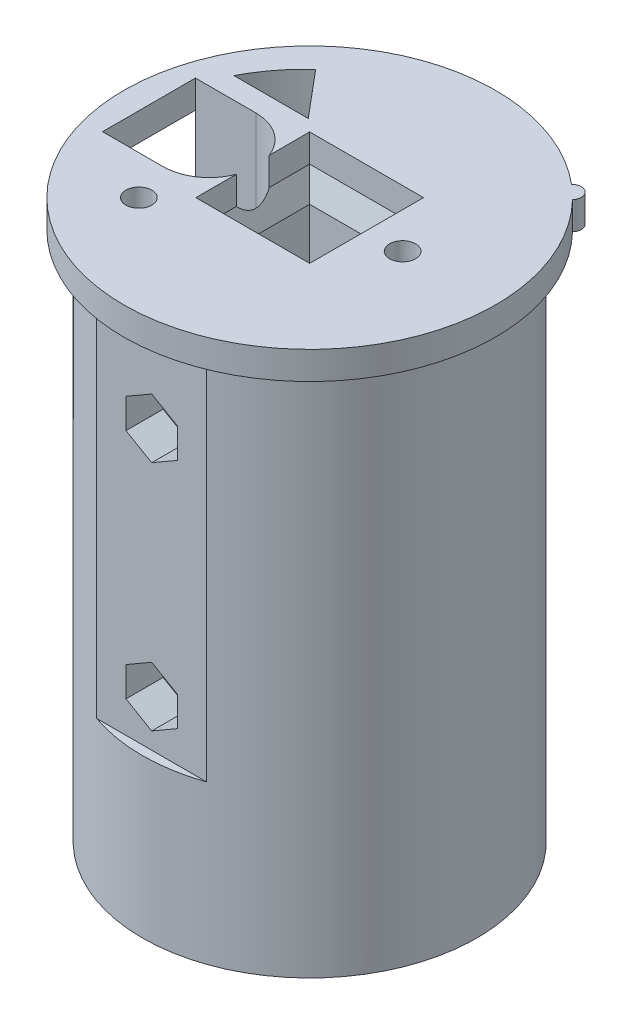
SolidWorks part; units mm, degrees
ref_plane "Спереди" through (0, 0, 0) normal (0, 0, 1) x (1, 0, 0)
ref_plane "Сверху" through (0, 0, 0) normal (0, 1, 0) x (1, 0, 0)
ref_plane "Справа" through (0, 0, 0) normal (1, 0, 0) x (0, 0, -1)
sketch "Sketch1" plane through (0, 0, 0) normal (0, 1, 0) x (1, 0, 0)
  line L0 (-5.125, 0) -> (-18, 0) construction
  line L1 (5.125, -5.125) -> (-5.125, -5.125)
  line L2 (5.125, -5.125) -> (5.125, 5.125)
  line L3 (5.125, 5.125) -> (-5.125, 5.125)
  line L4 (-5.125, -5.125) -> (-5.125, 5.125)
  line L5 (5.125, -5.125) -> (-5.125, 5.125) construction
  line L6 (5.125, 5.125) -> (-5.125, -5.125) construction
  circle A0 centre (0, 0) radius 18
  circle A1 centre (-12, 0) radius 2
  dimension "D1" = 36
  dimension "D3" = 6
  dimension "D2" = 10.25
extrude "Boss-Extrude1" add sketch "Sketch1" along normal blind 57
sketch "Sketch2" plane through (0, 57, 0) normal (0, 1, 0) x (1, 0, 0)
  line L0 (-10.8, 5) -> (-17.2916, 5)
  line L1 (-10.8, -5) -> (-17.2916, -5)
  line L2 (-5.125, 0) -> (-18, 0) construction
  line L3 (-5.125, 5.125) -> (-5.125, -5.125) construction
  circle A1 centre (0, 0) radius 18 construction
  arc A2 (-17.2916, 5) -> (-17.2916, -5) centre (0, 0) ccw
  arc A3 (-10.8, 5) -> (-10.8, -5) centre (-10.8, 0) cw
  point P12 (-5.8, 0)
  dimension "D1" = 5
extrude "Cut-Extrude1" cut sketch "Sketch2" against normal blind 25
sketch "Sketch4" plane through (0, 0, 0) normal (0, -1, 0) x (-1, 0, 0)
  line L0 (0, 0) -> (18, 21.4516) construction
  line L1 (0, 0) -> (18, -21.4516) construction
  line L2 (18, 21.4516) -> (18, -21.4516) construction
  line L3 (0, 0) -> (13.6996, 11.6756) construction
  line L4 (0, 0) -> (13.6996, -11.6756) construction
  line L5 (0, 0) -> (18, 0) construction
  line L6 (5.125, 5.125) -> (5.125, -5.125) construction
  line L7 (11.5702, 13.7888) -> (5.1423, 6.1284) construction
  line L8 (5.1423, 6.1284) -> (5.1423, -4.3826) construction
  line L9 (5.1423, -4.3826) -> (13.6996, -11.6756) construction
  line L10 (5.1423, 0.8729) -> (18.1354, 0.8729) construction
  line L12 (15.8104, 5.5479) -> (6.4604, 5.5479)
  line L13 (15.8104, 5.5479) -> (15.8104, -3.8021)
  line L14 (15.8104, -3.8021) -> (6.4604, -3.8021)
  line L15 (6.4604, 5.5479) -> (6.4604, -3.8021)
  line L16 (15.8104, 5.5479) -> (6.4604, -3.8021) construction
  line L17 (15.8104, -3.8021) -> (6.4604, 5.5479) construction
  arc A0 (13.6996, -11.6756) -> (11.5702, 13.7888) centre (0.5154, 0.0431) ccw construction
  circle A2 centre (0, 0) radius 18 construction
  point P2 (11, 0)
  point P5 (11.5702, 13.7888)
  point P7 (4.1157, 3.5076)
  point P8 (11.5702, -13.7888)
  point P11 (5.125, -6.1077)
  point P16 (11.1354, 0.8729)
  dimension "D5" = 10
  dimension "D1" = 100
  dimension "D2" = 3
  dimension "D3" = 3
  dimension "D4" = 9.35
  dimension "D6" = 7
extrude "Cut-Extrude3" cut sketch "Sketch4" against normal blind 20.4
sketch "Sketch5" plane through (0, 57, 0) normal (0, 1, 0) x (1, 0, 0)
  line L0 (0, 18) -> (0, -18) construction
  line L1 (5.9161, 17) -> (-5.9161, 17)
  line L2 (5.9161, -17) -> (-5.9161, -17)
  circle A0 centre (0, 0) radius 18 construction
  arc A1 (5.9161, 17) -> (-5.9161, 17) centre (0, 0) ccw
  arc A2 (5.9161, -17) -> (-5.9161, -17) centre (0, 0) cw
  point P11 (0, 17)
  dimension "D1" = 1
extrude "Cut-Extrude4" cut sketch "Sketch5" against normal blind 40
sketch "Sketch6" plane through (0, 0, -17) normal (0, 0, -1) x (-1, 0, 0)
  line L0 (0, 57) -> (0, 0) construction
  line L1 (5.9161, 57) -> (-5.9161, 57) construction
  line L2 (5.9161, 17) -> (-5.9161, 17) construction
  line L3 (5.9161, 0) -> (-5.9161, 0) construction
  circle A0 centre (0, 47) radius 1.5
  circle A1 centre (0, 22) radius 1.5
  dimension "D1" = 3
  dimension "D2" = 10
  dimension "D3" = 5
extrude "Cut-Extrude5" cut sketch "Sketch6" against normal through all
sketch "Sketch7" plane through (0, 0, -17) normal (0, 0, -1) x (-1, 0, 0)
  circle A0 centre (0, 47) radius 3
  circle A1 centre (0, 22) radius 3
  dimension "D1" = 6
extrude "Cut-Extrude6" cut sketch "Sketch7" against normal blind 3
sketch "Sketch8" plane through (0, 0, 17) normal (0, 0, 1) x (1, 0, 0)
  line L0 (5.9161, 17) -> (5.9161, 57) construction
  line L1 (0, 43.8) -> (2.7713, 45.4)
  line L2 (2.7713, 45.4) -> (2.7713, 48.6)
  line L3 (2.7713, 48.6) -> (0, 50.2)
  line L4 (0, 50.2) -> (-2.7713, 48.6)
  line L5 (-2.7713, 48.6) -> (-2.7713, 45.4)
  line L6 (-2.7713, 45.4) -> (0, 43.8)
  line L9 (0, 18.8) -> (2.7713, 20.4)
  line L10 (2.7713, 20.4) -> (2.7713, 23.6)
  line L11 (2.7713, 23.6) -> (0, 25.2)
  line L12 (0, 25.2) -> (-2.7713, 23.6)
  line L13 (-2.7713, 23.6) -> (-2.7713, 20.4)
  line L14 (-2.7713, 20.4) -> (0, 18.8)
  circle A0 centre (0, 47) radius 3.2 construction
  circle A1 centre (0, 22) radius 3.2 construction
  dimension "D1" = 6.4
extrude "Cut-Extrude7" cut sketch "Sketch8" against normal blind 4
chamfer "Chamfer1" distance 1 angle 70 4 edges at (-5.125, 57, 0) (0, 57, -5.125) (0, 57, 5.125) (5.125, 57, 0) first distance on face at (-5.2523, 57, 0)
sketch "Sketch9" plane through (0, 0, 0) normal (0, -1, 0) x (1, 0, 0)
  line L0 (16.4542, -7.2979) -> (-16.4542, -7.2979) construction
  line L1 (-15.8104, -5.5479) -> (-6.4604, -5.5479) construction
  line L2 (-7.4542, -7.2979) -> (-15.4542, -7.2979)
  line L3 (-7.4542, -7.2979) -> (-11.6323, -12.2772)
  line L4 (5.125, -5.125) -> (-5.125, -5.125) construction
  circle A0 centre (0, 0) radius 18 construction
  arc A1 (-15.4542, -7.2979) -> (-11.6323, -12.2772) centre (0.5168, 1.0043) ccw
  point P10 (-11.4542, -7.2979)
  dimension "D8" = 18
  dimension "D1" = 1.75
  dimension "D2" = 5
  dimension "D3" = 6.5
  dimension "D4" = 50
  dimension "D5" = 8
  dimension "D6" = 2.1729
  dimension "D7" = 23.9084
extrude "Cut-Extrude8" cut sketch "Sketch9" against normal through all
sketch "Sketch12" plane through (0, 57, 0) normal (0, 1, 0) x (1, 0, 0)
  line L0 (18, 0) -> (-10.8, 0) construction
  line L1 (0, 0) -> (-12.7279, -12.7279) construction
  arc A0 (5.9161, -17) -> (5.9161, 17) centre (0, 0) ccw construction
  arc A1 (-17.2916, -5) -> (-5.9161, -17) centre (0, 0) ccw construction
  circle A2 centre (10, 0) radius 1.4
  circle A3 centre (-9.1924, -9.1924) radius 1.4
  dimension "D1" = 2.8
  dimension "D2" = 10
  dimension "D3" = 13
extrude "Cut-Extrude10" cut sketch "Sketch12" against normal blind 20
sketch "Sketch13" plane through (0, 57, 0) normal (0, 1, 0) x (1, 0, 0)
  line L0 (-10.8, 5) -> (-17.2916, 5)
  line L1 (-6.125, 6.125) -> (6.125, 6.125)
  line L2 (-7.4542, 7.2979) -> (-15.4542, 7.2979)
  line L3 (-6.125, -6.125) -> (6.125, -6.125)
  line L4 (6.125, 6.125) -> (6.125, -6.125)
  line L5 (-6.125, 6.125) -> (6.125, -6.125) construction
  line L6 (-6.125, -6.125) -> (6.125, 6.125) construction
  line L7 (-17.2916, -5) -> (-10.8, -5)
  line L8 (-17.2916, 5) -> (-17.2916, -5)
  line L9 (-6.125, 1.7732) -> (-6.125, 6.125)
  line L10 (-6.125, -1.7732) -> (-6.125, -6.125)
  line L11 (-7.4542, 7.2979) -> (-11.6323, 12.2772)
  circle A0 centre (0, 0) radius 20
  arc A1 (-10.8, 5) -> (-6.125, 1.7732) centre (-10.8, 0) cw
  arc A2 (-6.125, -1.7732) -> (-10.8, -5) centre (-10.8, 0) cw
  circle A3 centre (10, 0) radius 1.4
  circle A4 centre (-9.1924, -9.1924) radius 1.4
  arc A5 (-11.6323, 12.2772) -> (-15.4542, 7.2979) centre (0.5168, -1.0043) ccw
  dimension "D1" = 40
extrude "Boss-Extrude2" add sketch "Sketch13" along normal blind 3
sketch "Sketch14" plane through (0, 60, 0) normal (0, 1, 0) x (1, 0, 0)
  line L0 (0, 0) -> (0, 20) construction
  line L1 (0, 0) -> (12.8558, 15.3209) construction
  line L2 (12.8558, 15.3209) -> (14.3216, 13.9603)
  circle A0 centre (0, 0) radius 20 construction
  arc A1 (12.8558, 15.3209) -> (14.3216, 13.9603) centre (13.5887, 14.6406) cw
  dimension "D2" = 1
  dimension "D1" = 40
  dimension "D3" = 2
extrude "Boss-Extrude3" add sketch "Sketch14" against normal up to surface (3 mm away) up to face at (0, 57, 20)
